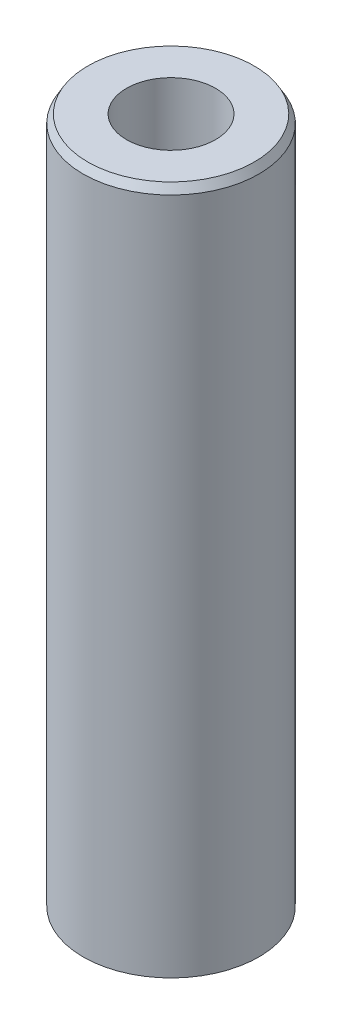
SolidWorks part; units mm, degrees
ref_plane "Front Plane" through (0, 0, 0) normal (0, 0, 1) x (1, 0, 0)
ref_plane "Top Plane" through (0, 0, 0) normal (0, 1, 0) x (1, 0, 0)
ref_plane "Right Plane" through (0, 0, 0) normal (1, 0, 0) x (0, 0, -1)
sketch "Sketch1" plane through (0, 0, 0) normal (0, 1, 0) x (1, 0, 0)
  circle A0 centre (0, 0) radius 42.5
  dimension "SHAFT_OD" = 85
extrude "Boss-Extrude1" add sketch "Sketch1" along normal blind 333.9356
sketch "Sketch2" plane through (0, 0, 0) normal (0, 1, 0) x (1, 0, 0)
  circle A0 centre (0, 0) radius 21.527
  dimension "BORE_D" = 43.054
extrude "Cut-Extrude1" cut sketch "Sketch2" along normal through all
chamfer "Chamfer1" distance 3.9009 angle 30 2 edges at (0, 333.9356, 42.5) (0, 0, 42.5) first distance on face at (0, 333.9356, 42.5) first distance on face at (0, 0, 21.527)
